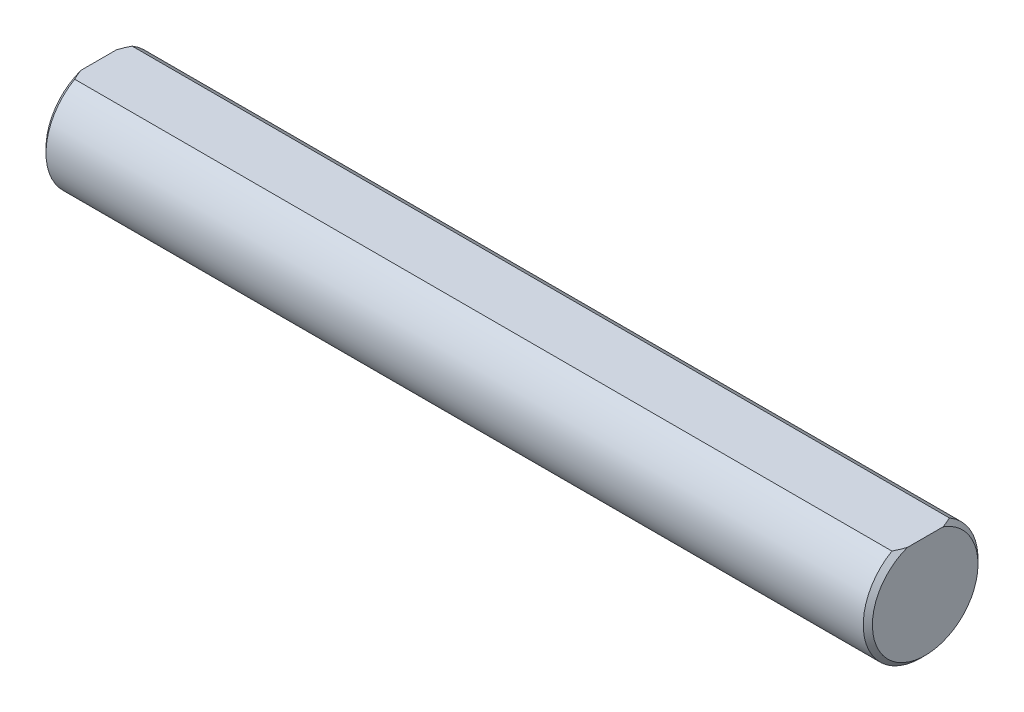
SolidWorks part; units mm, degrees
material "AISI 1045 Steel, cold drawn"
ref_plane "Front Plane" through (0, 0, 0) normal (0, 0, 1) x (1, 0, 0)
ref_plane "Top Plane" through (0, 0, 0) normal (0, 1, 0) x (1, 0, 0)
ref_plane "Right Plane" through (0, 0, 0) normal (1, 0, 0) x (0, 0, -1)
sketch "Sketch1" plane through (0, 0, 0) normal (1, 0, 0) x (0, 0, -1)
  circle A2 centre (0, 0) radius 3.175
  dimension "D1" = 6.35
extrude "Boss-Extrude1" add sketch "Sketch1" along normal blind 45.72
chamfer "Chamfer1" distance 0.254 angle 45 2 edges at (45.72, 0, -3.175) (0, 0, -3.175)
sketch "Sketch2" plane through (45.72, 0, 0) normal (1, 0, 0) x (0, 0, -1)
  line L0 (-1.5875, 2.7496) -> (1.5875, 2.7496)
  circle A0 centre (0, 0) radius 3.175 construction
  arc A1 (1.5875, 2.7496) -> (-1.5875, 2.7496) centre (0, 0) ccw
  dimension "D1" = 3.175
extrude "Cut-Extrude2" cut sketch "Sketch2" against normal through all
